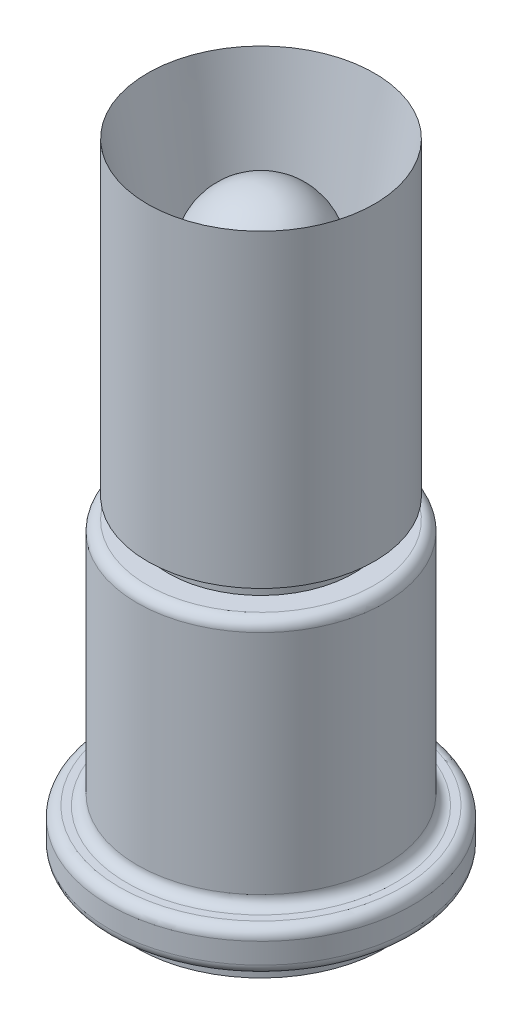
SolidWorks part; units mm, degrees
ref_plane "Front Plane" through (0, 0, 0) normal (0, 0, 1) x (1, 0, 0)
ref_plane "Top Plane" through (0, 0, 0) normal (0, 1, 0) x (1, 0, 0)
ref_plane "Right Plane" through (0, 0, 0) normal (1, 0, 0) x (0, 0, -1)
sketch "Sketch1" plane through (0, 0, 0) normal (1, 0, 0) x (0, 0, -1)
  line L0 (0, 0) -> (3.68, 0)
  line L1 (3.68, 0) -> (3.68, 1)
  line L2 (3.68, 1) -> (3, 1)
  line L3 (3, 1) -> (3, 7)
  line L4 (3, 7) -> (2.25, 7)
  line L5 (2.25, 7) -> (2.25, 7.5)
  line L6 (2.25, 7.5) -> (2.75, 7.5)
  line L7 (2.75, 7.5) -> (2.75, 15)
  line L8 (2.75, 15) -> (0, 15)
  line L9 (0, 15) -> (0, 0)
  point P3 (0, 0)
  dimension "D1" = 1
  dimension "D2" = 3
  dimension "D3" = 0.5
  dimension "D4" = 0.5
  dimension "D5" = 3.68
  dimension "D6" = 15
  dimension "D7" = 6
  dimension "D8" = 2.75
revolve "Revolve1" add sketch "Sketch1" angle 360 about L9
sketch "Sketch2" plane through (0, 0, 0) normal (1, 0, 0) x (0, 0, -1)
  line L1 (0, 0) -> (3, 0)
  line L2 (0, 0) -> (0, -0.5)
  line L3 (0, -0.5) -> (3, -0.5)
  line L4 (3, 0) -> (3, -0.5)
  line L5 (3, 1) -> (3, 7) construction
  dimension "D1" = 0.5
revolve "Revolve2" add sketch "Sketch2" angle 360 about L2
sketch "Sketch3" plane through (0, 0, 0) normal (1, 0, 0) x (0, 0, -1)
  line L1 (2.75, 15) -> (-2.75, 15) construction
  line L2 (0, -1) -> (0, 1)
  arc A0 (0, -1) -> (0, 1) centre (0, 0) ccw
  point P4 (0, -1)
  dimension "D1" = 16
revolve "Revolve3" add sketch "Sketch3" angle 360 about L2
fillet "Fillet1" radius 0.25 4 edges at (0, 0, 3.68) (0, 1, 3.68) (0, 7, 3) (0, 1, 3)
sketch "Sketch5" plane through (0, 0, 0) normal (1, 0, 0) x (0, 0, -1)
  line L0 (0, 15) -> (0, 8)
  line L1 (2.75, 15) -> (-2.75, 15) construction
  line L2 (0, 8) -> (1.5, 8)
  line L3 (1.5, 8) -> (2.75, 15)
  line L4 (2.75, 15) -> (0, 15)
  line L5 (-2.75, 7.5) -> (2.75, 7.5) construction
  dimension "D1" = 1.5
  dimension "D2" = 0.5
revolve "Cut-Revolve1" cut sketch "Sketch5" angle 360 about L0
sketch "Sketch6" plane through (0, 0, 0) normal (1, 0, 0) x (0, 0, -1)
  line L0 (1.5, 8) -> (-1.5, 8) construction
  line L1 (0, 8) -> (0, 12.5)
  line L2 (-2.75, 15) -> (2.75, 15) construction
  line L3 (1.5, 8) -> (1.5, 12.5)
  line L4 (0, 12.5) -> (0, 14)
  line L5 (0, 8) -> (1.5, 8)
  arc A0 (1.5, 12.5) -> (0, 14) centre (0, 12.5) ccw
  point P6 (0, 14)
  dimension "D1" = 3
  dimension "D2" = 1
revolve "Revolve4" add sketch "Sketch6" angle 360 about L1
